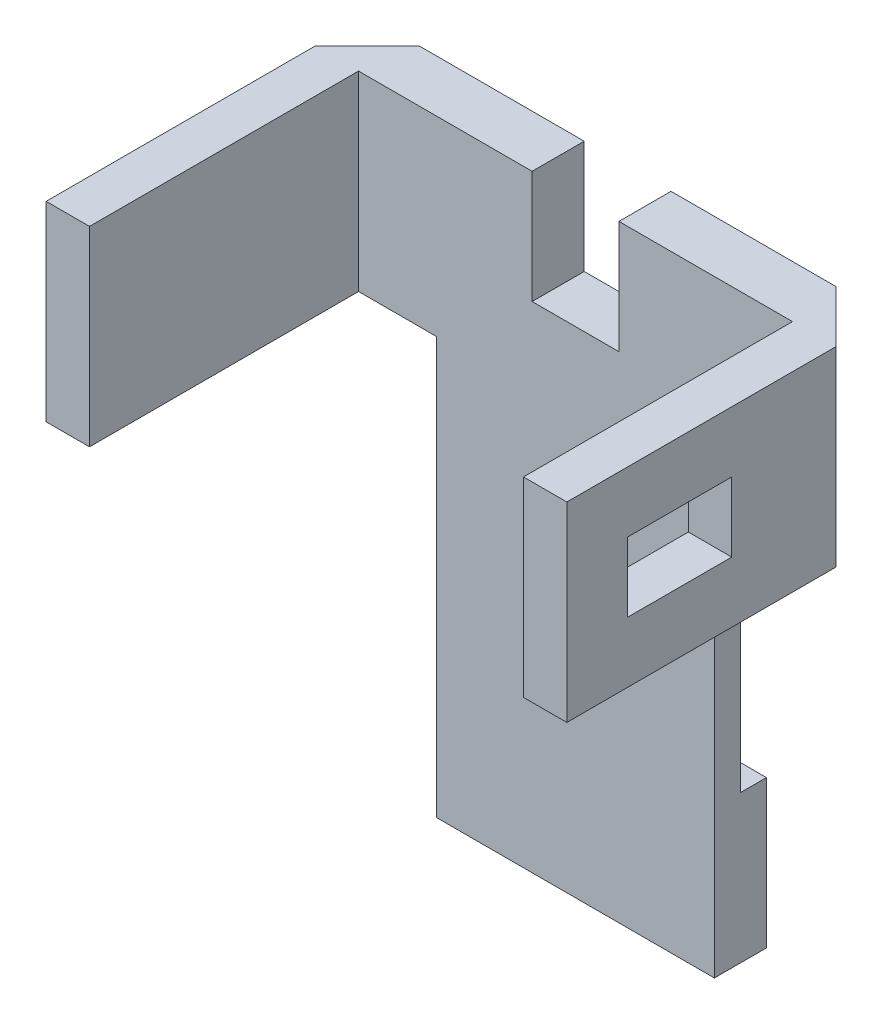
SolidWorks part; units mm, degrees
ref_plane "Спереди" through (0, 0, 0) normal (0, 0, 1) x (1, 0, 0)
ref_plane "Сверху" through (0, 0, 0) normal (0, 1, 0) x (1, 0, 0)
ref_plane "Справа" through (0, 0, 0) normal (1, 0, 0) x (0, 0, -1)
sketch "Эскиз1" plane through (0, 0, 0) normal (0, 0, 1) x (1, 0, 0)
  line L1 (-15, -35) -> (15, -35)
  line L2 (-15, -35) -> (-15, 35)
  line L3 (-15, 35) -> (15, 35)
  line L4 (15, -35) -> (15, 35)
  line L5 (-15, -35) -> (15, 35) construction
  line L6 (-15, 35) -> (15, -35) construction
  line L7 (15, -35) -> (1, -35)
  line L8 (15, -35) -> (15, 13)
  line L9 (15, 13) -> (1, 13)
  line L10 (1, -35) -> (1, 13)
  line L11 (-15, 35) -> (-10, 35)
  line L12 (-15, 35) -> (-15, 22)
  line L13 (-15, 22) -> (-10, 22)
  line L14 (-10, 35) -> (-10, 22)
  point P0 (0, 0)
  dimension "D1" = 30
  dimension "D2" = 70
  dimension "D3" = 48
  dimension "D4" = 14
  dimension "D5" = 13
  dimension "D6" = 5
extrude "Бобышка-Вытянуть1" add sketch "Эскиз1" along normal blind 6 contours L3 L14 L13 L2 L1 L10 L9 L4 region at (-3.3481, 4.0642, 0)
sketch "Эскиз2" plane through (0, 0, 6) normal (0, 0, 1) x (1, 0, 0)
  line L0 (-10, 35) -> (15, 35) construction
  line L1 (15, 13) -> (10, 13)
  line L2 (15, 13) -> (15, 35)
  line L3 (15, 35) -> (10, 35)
  line L4 (10, 13) -> (10, 35)
  dimension "D1" = 5
extrude "Бобышка-Вытянуть2" add sketch "Эскиз2" along normal blind 31
chamfer "Фаска1" distance 6 angle 45 1 edges at (15, 24, 0)
sketch "Эскиз3" plane through (10, 0, 0) normal (-1, 0, 0) x (0, 0, 1)
  line L0 (37, 24) -> (6, 24) construction
  line L1 (18, 28) -> (30, 28)
  line L2 (18, 28) -> (18, 20)
  line L3 (18, 20) -> (30, 20)
  line L4 (30, 28) -> (30, 20)
  line L5 (18, 28) -> (30, 20) construction
  line L6 (18, 20) -> (30, 28) construction
  line L7 (37, 35) -> (37, 13) construction
  line L8 (6, 35) -> (6, 13) construction
  point P0 (24, 24)
  dimension "D1" = 8
  dimension "D2" = 12
  dimension "D3" = 7
extrude "Вырез-Вытянуть1" cut sketch "Эскиз3" against normal through all
sketch "Эскиз4" plane through (-15, 0, 0) normal (-1, 0, 0) x (0, 0, 1)
  line L0 (0, -35) -> (0, 22) construction
  line L1 (3, -18) -> (0, -18)
  line L2 (3, -18) -> (3, 3)
  line L3 (3, 3) -> (0, 3)
  line L4 (0, -18) -> (0, 3)
  line L5 (3, -18) -> (0, 3) construction
  line L6 (3, 3) -> (0, -18) construction
  line L7 (6, -35) -> (0, -35) construction
  point P0 (1.5, -7.5)
  dimension "D1" = 21
  dimension "D2" = 17
  dimension "D3" = 3
extrude "Вырез-Вытянуть2" cut sketch "Эскиз4" against normal through all
mirror "Зеркальное отражение1" about plane through (-15, 0, 6) normal (-1, 0, 0) of "Вырез-Вытянуть2", "Бобышка-Вытянуть1", "Бобышка-Вытянуть2", "Фаска1"
